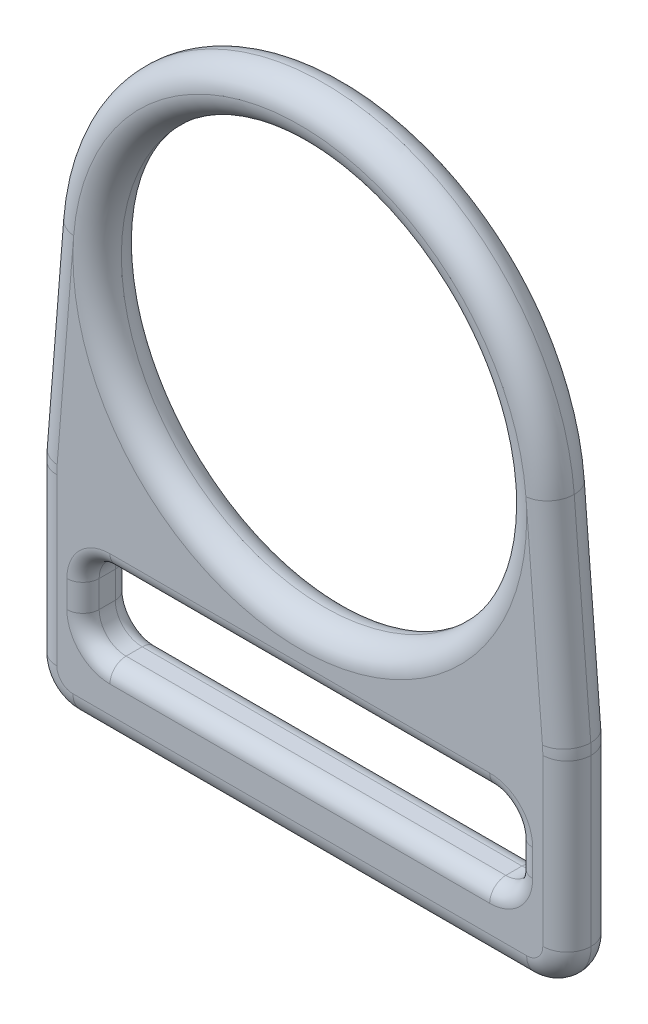
SolidWorks part; units mm, degrees
ref_plane "Front Plane" through (0, 0, 0) normal (0, 0, 1) x (1, 0, 0)
ref_plane "Top Plane" through (0, 0, 0) normal (0, 1, 0) x (1, 0, 0)
ref_plane "Right Plane" through (0, 0, 0) normal (1, 0, 0) x (0, 0, -1)
sketch "Sketch2" plane through (0, 0, 0) normal (1, 0, 0) x (0, 0, -1)
  circle A0 centre (0, 0) radius 2.286
  dimension "D1" = 4.572
sketch "Sketch3" plane through (0, 0, 0) normal (0, 0, 1) x (1, 0, 0)
  circle A0 centre (0, -21.4312) radius 21.4312
  dimension "D1" = 42.8625
sweep "Sweep1" add profiles "Sketch2" path "Sketch3"
sketch "Sketch4" plane through (0, 0, 0) normal (0, 0, 1) x (1, 0, 0)
  line L0 (-23.6421, -19.5444) -> (-25.201, -39.078)
  line L1 (-25.2412, -40.0883) -> (-25.2412, -55.7213)
  line L2 (-21.4312, -59.5312) -> (21.4312, -59.5312)
  line L3 (25.2412, -55.7213) -> (25.2412, -40.0883)
  line L4 (25.201, -39.078) -> (23.6421, -19.5444)
  line L5 (-20.4788, -48.1013) -> (-20.4788, -50.6412)
  line L6 (-17.9387, -53.1812) -> (17.9387, -53.1812)
  line L7 (20.4788, -50.6412) -> (20.4788, -48.1013)
  line L8 (17.9387, -45.5613) -> (-17.9387, -45.5613)
  line L9 (0, -21.4312) -> (0, -59.5312) construction
  arc A2 (21.4312, -59.5312) -> (25.2412, -55.7213) centre (21.4312, -55.7213) ccw
  arc A3 (-25.2412, -55.7213) -> (-21.4312, -59.5312) centre (-21.4312, -55.7213) ccw
  arc A4 (20.4788, -48.1013) -> (17.9387, -45.5613) centre (17.9387, -48.1013) ccw
  arc A5 (17.9387, -53.1812) -> (20.4788, -50.6412) centre (17.9387, -50.6412) ccw
  arc A6 (-20.4788, -50.6412) -> (-17.9387, -53.1812) centre (-17.9387, -50.6412) ccw
  arc A7 (-20.4788, -48.1013) -> (-17.9387, -45.5613) centre (-17.9387, -48.1013) cw
  arc A8 (25.2412, -40.0883) -> (25.201, -39.078) centre (12.5412, -40.0883) ccw
  arc A9 (-25.201, -39.078) -> (-25.2412, -40.0883) centre (-12.5412, -40.0883) ccw
  circle A10 centre (0, -21.4312) radius 23.7172 construction
  arc A11 (23.6421, -19.5444) -> (-23.6421, -19.5444) centre (0, -21.4312) ccw
  circle A12 centre (0, -21.4312) radius 19.1453 construction
  circle A13 centre (0, -21.4312) radius 19.1453
  point P30 (0, 2.286)
  dimension "D1" = 3.81
  dimension "D2" = 2.54
  dimension "D3" = 12.7
  dimension "D4" = 6.35
  dimension "D5" = 4.7625
  dimension "D6" = 42.8625
  dimension "D7" = 7.62
  dimension "D8" = 38.1
  dimension "D9" = 19.5335
extrude "Boss-Extrude1" add sketch "Sketch4" along normal through all and the other way through all
fillet "Fillet1" radius 2.286 22 edges at (24.4215, -29.3112, 2.286) (25.2312, -39.5827, 2.286) (25.2413, -47.9048, 2.286) (24.1253, -58.4153, 2.286) (0, -59.5312, 2.286) (-24.1253, -58.4153, 2.286) (-25.2412, -47.9048, 2.286) (-25.2312, -39.5827, 2.286) (-24.4215, -29.3112, 2.286) (24.4215, -29.3112, -2.286) (25.2312, -39.5827, -2.286) (25.2413, -47.9048, -2.286) (24.1253, -58.4153, -2.286) (0, -59.5312, -2.286) (-24.1253, -58.4153, -2.286) (-25.2412, -47.9048, -2.286) (-25.2312, -39.5827, -2.286) (-24.4215, -29.3112, -2.286) (19.1453, -21.4312, 2.286) (19.1453, -21.4312, -2.286) (0, 2.286, 2.286) (0, 2.286, -2.286)
fillet "Fillet2" radius 1.524 16 edges at (-19.7348, -52.4373, 2.286) (-20.4787, -49.3713, 2.286) (-19.7348, -46.3052, 2.286) (0, -45.5613, 2.286) (19.7348, -46.3052, 2.286) (20.4788, -49.3713, 2.286) (19.7348, -52.4373, 2.286) (-19.7348, -52.4373, -2.286) (-20.4787, -49.3713, -2.286) (-19.7348, -46.3052, -2.286) (0, -45.5613, -2.286) (19.7348, -46.3052, -2.286) (20.4788, -49.3713, -2.286) (19.7348, -52.4373, -2.286) (0, -53.1812, 2.286) (0, -53.1812, -2.286)
ref_point "Point1" parameters "D1"=30.1625
ref_point "Point2" parameters "D1"=30.48
sketch "Sketch5" plane through (0, -53.1812, 0) normal (0, 1, 0) x (1, 0, 0)
  line L0 (-17.9387, 0) -> (17.9387, 0) construction
  line L1 (-17.9387, -0.762) -> (-17.9387, 0.762) construction
  line L2 (17.9387, -0.762) -> (17.9387, 0.762) construction
ref_axis "Axis1" through (-17.9387, -53.1812, 0) along (1, 0, 0)
sketch "Sketch6" plane through (0, 0, 0) normal (0, 0, 1) x (1, 0, 0)
  line L0 (0, 0) -> (0, -21.4312) construction
  circle A0 centre (0, -21.4312) radius 19.1453 construction
  circle A1 centre (0, -21.4312) radius 19.1453
  point P3 (-7.9375, -4.0089)
  point P4 (7.9375, -4.0089)
  point P6 (0, 0)
  point P8 (0, 0)
  dimension "D1" = 15.875
ref_point "Point3"
ref_point "Point4"
ref_point "Point5"
